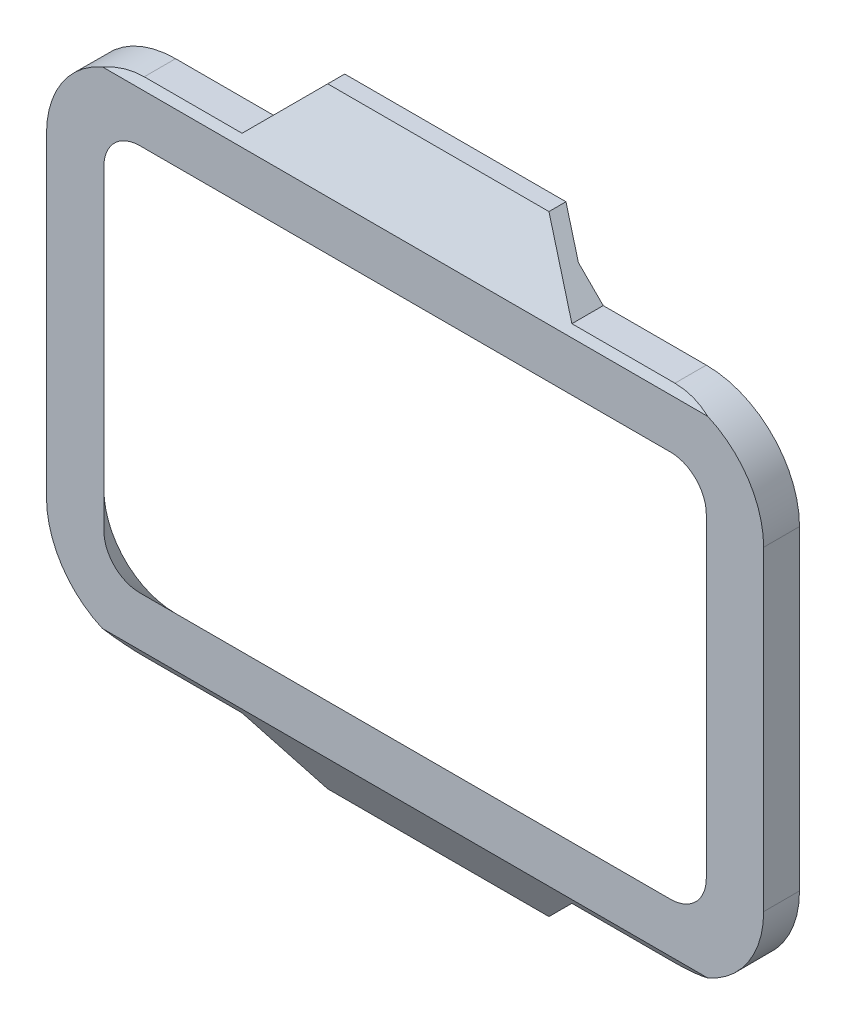
SolidWorks part; units mm, degrees
ref_plane "Front Plane" through (0, 0, 0) normal (0, 0, 1) x (1, 0, 0)
ref_plane "Top Plane" through (0, 0, 0) normal (0, 1, 0) x (1, 0, 0)
ref_plane "Right Plane" through (0, 0, 0) normal (1, 0, 0) x (0, 0, -1)
sketch "Sketch1" plane through (0, 0, 0) normal (0, 0, 1) x (1, 0, 0)
  line L0 (-28.9884, -88.0987) -> (45.0116, -88.0987)
  line L1 (58.0116, -75.0987) -> (58.0116, -31.0987)
  line L2 (45.0116, -18.0987) -> (-28.9884, -18.0987)
  line L3 (-41.9884, -31.0987) -> (-41.9884, -75.0987)
  line L4 (-28.9884, -80.0987) -> (45.0116, -80.0987)
  line L5 (50.0116, -75.0987) -> (50.0116, -31.0987)
  line L6 (45.0116, -26.0987) -> (-28.9884, -26.0987)
  line L7 (-33.9884, -31.0987) -> (-33.9884, -75.0987)
  line L24 (55.0116, -75.0987) -> (55.0116, -31.0987)
  line L25 (45.0116, -21.0987) -> (-28.9884, -21.0987)
  line L26 (-38.9884, -31.0987) -> (-38.9884, -75.0987)
  line L27 (-28.9884, -85.0987) -> (45.0116, -85.0987)
  line L28 (55.0116, -75.0987) -> (55.0116, -31.0987)
  line L29 (45.0116, -21.0987) -> (-28.9884, -21.0987)
  line L30 (-38.9884, -31.0987) -> (-38.9884, -75.0987)
  line L31 (-28.9884, -85.0987) -> (45.0116, -85.0987)
  arc A0 (45.0116, -88.0987) -> (58.0116, -75.0987) centre (45.0116, -75.0987) ccw
  arc A1 (58.0116, -31.0987) -> (45.0116, -18.0987) centre (45.0116, -31.0987) ccw
  arc A2 (-28.9884, -18.0987) -> (-41.9884, -31.0987) centre (-28.9884, -31.0987) ccw
  arc A3 (-41.9884, -75.0987) -> (-28.9884, -88.0987) centre (-28.9884, -75.0987) ccw
  arc A4 (45.0116, -80.0987) -> (50.0116, -75.0987) centre (45.0116, -75.0987) ccw
  arc A5 (50.0116, -31.0987) -> (45.0116, -26.0987) centre (45.0116, -31.0987) ccw
  arc A6 (-28.9884, -26.0987) -> (-33.9884, -31.0987) centre (-28.9884, -31.0987) ccw
  arc A7 (-33.9884, -75.0987) -> (-28.9884, -80.0987) centre (-28.9884, -75.0987) ccw
  arc A20 (45.0116, -85.0987) -> (55.0116, -75.0987) centre (45.0116, -75.0987) ccw
  arc A21 (55.0116, -31.0987) -> (45.0116, -21.0987) centre (45.0116, -31.0987) ccw
  arc A22 (-28.9884, -21.0987) -> (-38.9884, -31.0987) centre (-28.9884, -31.0987) ccw
  arc A23 (-38.9884, -75.0987) -> (-28.9884, -85.0987) centre (-28.9884, -75.0987) ccw
  arc A24 (45.0116, -85.0987) -> (55.0116, -75.0987) centre (45.0116, -75.0987) ccw
  arc A25 (55.0116, -31.0987) -> (45.0116, -21.0987) centre (45.0116, -31.0987) ccw
  arc A26 (-28.9884, -21.0987) -> (-38.9884, -31.0987) centre (-28.9884, -31.0987) ccw
  arc A27 (-38.9884, -75.0987) -> (-28.9884, -85.0987) centre (-28.9884, -75.0987) ccw
  dimension "D1" = 0.3
  dimension "D2" = 3
  dimension "D3" = 5
extrude "Boss-Extrude1" add sketch "Sketch1" against normal blind 5 contours L30 A27 L31 A24 L28 A25 L29 A26 A7 L7 A6 L6 A5 L5 A4 L4 | L3 A3 L0 A0 L1 A1 L2 A2 A27 L30 A26 L29 A25 L28 A24 L31
chamfer "Chamfer1" distance 5 angle 45 8 edges at (8.0116, -80.0987, -5) (48.5471, -78.6342, -5) (-32.524, -78.6342, -5) (50.0116, -53.0987, -5) (-33.9884, -53.0987, -5) (48.5471, -27.5632, -5) (-32.524, -27.5632, -5) (8.0116, -26.0987, -5)
sketch "Sketch2" plane through (0, 0, 0) normal (0, 0, 1) x (1, 0, 0)
  line L0 (-15.3454, -18.0987) -> (-7.7744, -10.5276)
  line L1 (45.0116, -18.0987) -> (-28.9884, -18.0987) construction
  line L2 (-7.7744, -10.5276) -> (23.0734, -10.5276)
  line L3 (23.0734, -10.5276) -> (30.6444, -18.0987)
  line L4 (30.6444, -18.0987) -> (-15.3454, -18.0987)
  dimension "D1" = 45
  dimension "D2" = 45
extrude "Boss-Extrude2" add sketch "Sketch2" against normal blind 8
chamfer "Chamfer2" distance 5 angle 60 2 edges at (7.6495, -18.0987, -8) (7.6495, -10.5276, 0)
ref_plane "Plane1" through (0, -53.0987, 0) normal (0, 1, 0) x (1, 0, 0)
mirror "Mirror1" about plane through (0, -53.0987, 0) normal (0, 1, 0) of "Chamfer2", "Boss-Extrude2"
sketch "Sketch5" plane through (0, 0, -30) normal (0, 0, -1) x (-1, 0, 0)
  line L0 (-53.7116, -31.0987) -> (-48.7847, -31.0987)
  line L1 (-48.7847, -31.0987) -> (-48.7847, -23.2595)
  arc A0 (-53.7104, -30.9563) -> (-53.7116, -31.0987) centre (-45.0116, -31.0987) ccw construction
  arc A1 (-53.7116, -31.0987) -> (-48.7847, -23.2595) centre (-45.0116, -31.0987) cw
